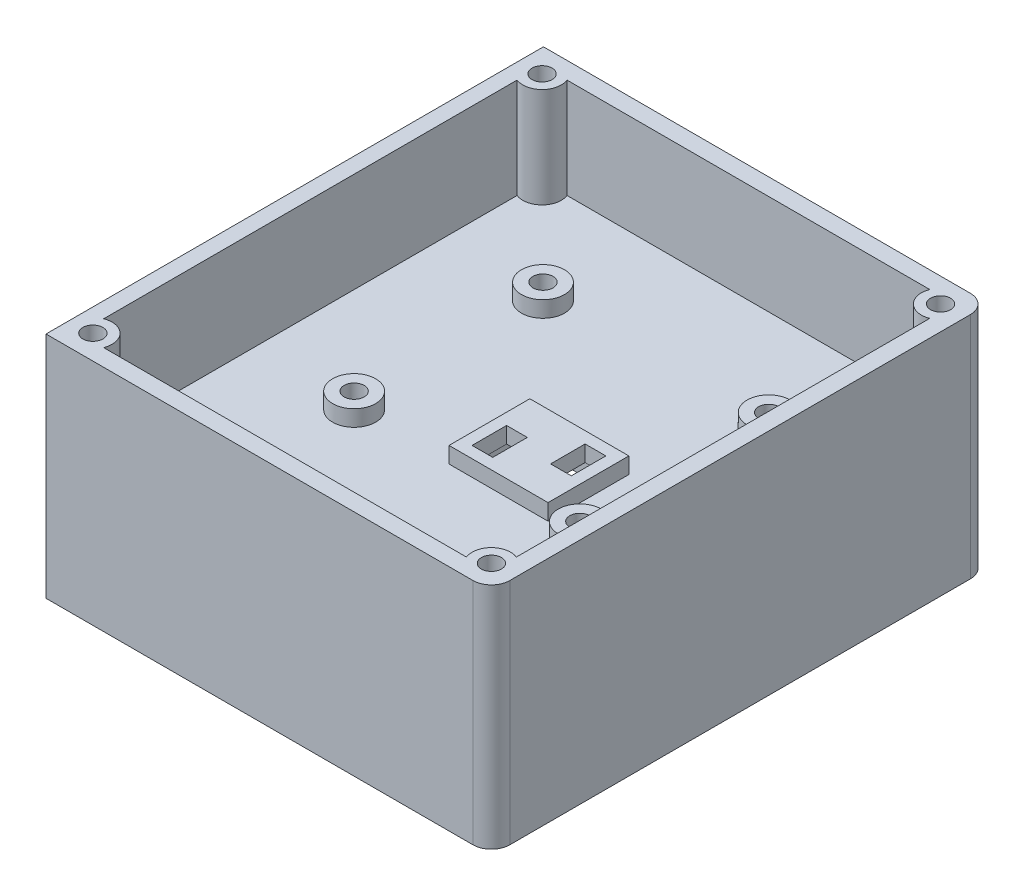
SolidWorks part; units mm, degrees
ref_plane "Front Plane" through (0, 0, 0) normal (0, 0, 1) x (1, 0, 0)
ref_plane "Top Plane" through (0, 0, 0) normal (0, 1, 0) x (1, 0, 0)
ref_plane "Right Plane" through (0, 0, 0) normal (1, 0, 0) x (0, 0, -1)
sketch "Sketch1" plane through (0, 0, 0) normal (0, 1, 0) x (1, 0, 0)
  line L1 (73.9904, 53.1) -> (166.6904, 53.1)
  line L2 (73.9904, 53.1) -> (73.9904, -54.9)
  line L3 (73.9904, -54.9) -> (166.6904, -54.9)
  line L4 (170.6904, 49.1) -> (170.6904, -50.9)
  line L6 (170.6904, -50.9) -> (170.6904, 49.1) construction
  line L7 (73.6904, 53.1) -> (73.6904, 45.1) construction
  line L8 (166.6904, 53.1) -> (73.6904, 53.1) construction
  line L9 (73.6904, -54.9) -> (166.6904, -54.9) construction
  line L10 (166.6904, -50.9) -> (166.6904, 49.1) construction
  line L11 (166.9904, 49.4) -> (77.3904, 49.4)
  line L12 (166.9904, 49.4) -> (166.9904, -51.2)
  line L13 (166.9904, -51.2) -> (77.3904, -51.2)
  line L14 (77.3904, 49.4) -> (77.3904, -51.2)
  line L15 (166.6904, 49.1) -> (77.6904, 49.1) construction
  line L16 (166.6904, 49.1) -> (77.6904, 49.1) construction
  line L17 (166.6904, -50.9) -> (166.6904, 49.1) construction
  arc A0 (166.6904, -54.9) -> (170.6904, -50.9) centre (166.6904, -50.9) ccw
  arc A1 (166.6904, 53.1) -> (170.6904, 49.1) centre (166.6904, 49.1) cw
  point P24 (122.1904, 49.1)
  point P25 (122.1904, 49.4)
  point P28 (166.6904, -0.9)
  point P29 (166.9904, -0.9)
  dimension "D4" = 4
  dimension "D1" = 0.3
  dimension "D2" = 0.3
  dimension "D3" = 0.3
extrude "Boss-Extrude1" add sketch "Sketch1" along normal up to surface (49.7 mm away)
sketch "Sketch4" plane through (77.3904, 0, 0) normal (1, 0, 0) x (0, 0, -1)
  line L0 (49.4, 0) -> (-51.2, 0) construction
  line L1 (28.8, 12) -> (45.4, 12)
  line L2 (28.8, 12) -> (28.8, 0)
  line L3 (28.8, 0) -> (45.4, 0)
  line L4 (45.4, 12) -> (45.4, 0)
  line L5 (29.1, 11.7) -> (29.1, -0.3) construction
  line L6 (29.1, 11.7) -> (45.1, 11.7) construction
  point P10 (37.1, 11.7)
  point P11 (37.1, 12)
  dimension "D1" = 0.3
  dimension "D2" = 0.3
extrude "Cut-Extrude1" cut sketch "Sketch4" against normal through all
sketch "Sketch5" plane through (77.3904, 0, 0) normal (1, 0, 0) x (0, 0, -1)
  line L0 (-51.2, 49.7) -> (-51.2, 0) construction
  line L1 (-51.2, 25) -> (49.4, 25)
  line L2 (-51.2, 25) -> (-51.2, 28)
  line L3 (-51.2, 28) -> (49.4, 28)
  line L4 (49.4, 25) -> (49.4, 28)
  line L5 (49.4, 49.7) -> (49.4, 0) construction
  line L6 (45.1, 24.7) -> (-46.9, 24.7) construction
  dimension "D1" = 3
  dimension "D2" = 0.3
extrude "Boss-Extrude2" add sketch "Sketch5" along normal up to surface (89.6 mm away) up to face at (166.9904, 24.85, 0.9)
sketch "Sketch7" plane through (0, 28, 0) normal (0, 1, 0) x (1, 0, 0)
  line L0 (77.3904, 49.4) -> (78.9283, 47.862) construction
  line L1 (166.9904, 49.4) -> (77.3904, 49.4) construction
  line L2 (77.3904, -0.9) -> (166.9904, -0.9) construction
  line L3 (77.3904, 49.4) -> (77.3904, -51.2) construction
  line L4 (166.9904, -51.2) -> (166.9904, 49.4) construction
  line L5 (122.1904, -51.2) -> (122.1904, 49.4) construction
  line L6 (166.9904, -51.2) -> (77.3904, -51.2) construction
  line L7 (166.9904, 49.4) -> (165.4524, 47.862) construction
  line L8 (166.9904, -51.2) -> (165.4524, -49.662) construction
  line L9 (77.3904, -51.2) -> (78.9283, -49.662) construction
  circle A0 centre (78.9283, 47.862) radius 2.175
  circle A1 centre (78.9283, 47.862) radius 4.175
  circle A2 centre (165.4524, 47.862) radius 4.175
  circle A3 centre (165.4524, 47.862) radius 2.175
  circle A4 centre (165.4524, -49.662) radius 2.175
  circle A5 centre (165.4524, -49.662) radius 4.175
  circle A6 centre (78.9283, -49.662) radius 4.175
  circle A7 centre (78.9283, -49.662) radius 2.175
  dimension "D1" = 4.35
  dimension "D2" = 2
  dimension "D3" = 45
extrude "Boss-Extrude3" add sketch "Sketch7" along normal up to surface (21.7 mm away) contours A6 | A1 | A2 | A5 up to face at (122.1904, 49.7, 0.9)
extrude "Cut-Extrude2" cut sketch "Sketch7<3>" against normal blind 5 from surface contours A0 | A3 | A4 | A7 starting at face at (122.1904, 49.7, 0.9)
sketch "Sketch7<3>" plane through (0, 28, 0) normal (0, 1, 0) x (1, 0, 0) same geometry as "Sketch7"
sketch "Sketch9" plane through (0, 28, 0) normal (0, 1, 0) x (1, 0, 0)
  line L0 (166.9904, -45.7806) -> (166.9904, 43.9806) construction
  line L1 (161.571, 49.4) -> (82.8097, 49.4) construction
  circle A0 centre (99.9904, 27) radius 2.175
  circle A1 centre (148.9904, 27) radius 2.175
  circle A2 centre (99.9904, -14) radius 2.175
  circle A3 centre (148.9904, -14) radius 2.175
  circle A4 centre (148.9904, -14) radius 4.675
  circle A5 centre (99.9904, -14) radius 4.675
  circle A6 centre (99.9904, 27) radius 4.675
  circle A7 centre (148.9904, 27) radius 4.675
  point P12 (0, 0)
  point P13 (0, 0)
  point P14 (0, 0)
  point P15 (29.3658, 27.8853)
  dimension "D1" = 4.35
  dimension "D2" = 2.5
  dimension "D4" = 22.4
  dimension "D3" = 18
  dimension "D5" = 49
  dimension "D6" = 41
extrude "Boss-Extrude4" add sketch "Sketch9" along normal blind 3.5
extrude "Cut-Extrude4" cut sketch "Sketch9<2>" against normal blind 1.5 contours A0 | A1 | A3 | A2
sketch "Sketch9<2>" plane through (0, 28, 0) normal (0, 1, 0) x (1, 0, 0) same geometry as "Sketch9"
sketch "Sketch11" plane through (0, 28, 0) normal (0, 1, 0) x (1, 0, 0)
  line L1 (127.4904, -3.9) -> (122.9904, -3.9)
  line L2 (127.4904, -3.9) -> (127.4904, -11.4)
  line L3 (127.4904, -11.4) -> (122.9904, -11.4)
  line L4 (122.9904, -3.9) -> (122.9904, -11.4)
  line L5 (134.9904, -6.35) -> (139.4904, -6.35)
  line L6 (134.9904, -6.35) -> (134.9904, 1.15)
  line L7 (134.9904, 1.15) -> (139.4904, 1.15)
  line L8 (139.4904, -6.35) -> (139.4904, 1.15)
  line L9 (120.4904, -13.9) -> (141.9904, -13.9)
  line L10 (120.4904, -13.9) -> (120.4904, 3.65)
  line L11 (120.4904, 3.65) -> (141.9904, 3.65)
  line L12 (141.9904, -13.9) -> (141.9904, 3.65)
  circle A0 centre (148.9904, -14) radius 2.175 construction
  circle A2 centre (148.9904, -14) radius 2.175 construction
  dimension "D1" = 7.5
  dimension "D2" = 4.5
  dimension "D3" = 2.45
  dimension "D4" = 7.5
  dimension "D5" = 2.5
  dimension "D6" = 2.5
  dimension "D7" = 2.5
  dimension "D8" = 2.5
  dimension "D9" = 21.5
  dimension "D10" = 17.55
  dimension "D11" = 7
  dimension "D12" = 0.1
extrude "Boss-Extrude5" add sketch "Sketch11" along normal up to surface (3.5 mm away) up to face at (148.9904, 31.5, 18.675)
sketch "Sketch12" plane through (0, 25, 0) normal (0, -1, 0) x (1, 0, 0)
  line L0 (122.9904, 11.4) -> (127.4904, 11.4) construction
  line L1 (122.7404, 11.65) -> (139.7404, 11.65)
  line L2 (122.7404, 11.65) -> (122.7404, -1.4)
  line L3 (122.7404, -1.4) -> (139.7404, -1.4)
  line L4 (139.7404, 11.65) -> (139.7404, -1.4)
  line L5 (122.9904, 3.9) -> (122.9904, 11.4) construction
  line L6 (139.4904, 6.35) -> (139.4904, -1.15) construction
  line L7 (139.4904, -1.15) -> (134.9904, -1.15) construction
  dimension "D1" = 0.25
  dimension "D2" = 0.25
  dimension "D3" = 0.25
  dimension "D4" = 0.25
extrude "Cut-Extrude5" cut sketch "Sketch12" against normal blind 3
equation "\"D6@Sketch11\"=\"D5@Sketch11\""
equation "\"D8@Sketch11\"=\"D7@Sketch11\""
